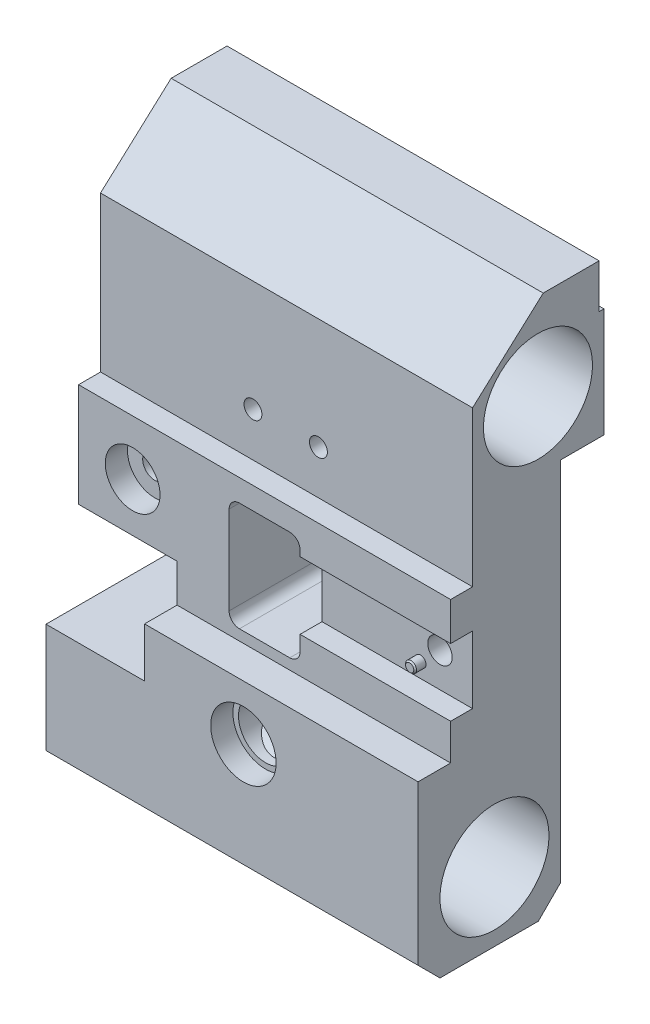
SolidWorks part; units mm, degrees
material "1060 Alloy"
ref_plane "Front Plane" through (0, 0, 0) normal (0, 0, 1) x (1, 0, 0)
ref_plane "Top Plane" through (0, 0, 0) normal (0, 1, 0) x (1, 0, 0)
ref_plane "Right Plane" through (0, 0, 0) normal (1, 0, 0) x (0, 0, -1)
sketch "Sketch1" plane through (0, 0, 0) normal (1, 0, 0) x (0, 0, -1)
  line L0 (14.15, 137.2) -> (30.37, 137.2)
  line L1 (30.37, 137.2) -> (30.37, 124.41)
  line L2 (30.37, 124.41) -> (31.79, 124.41)
  line L3 (31.79, 124.41) -> (31.79, 92.72)
  line L4 (31.79, 92.72) -> (19.1, 92.72)
  line L5 (19.1, 92.72) -> (19.1, -13.636)
  line L6 (19.1, -13.636) -> (12.736, -20)
  line L7 (12.736, -20) -> (-15.816, -20)
  line L8 (-15.816, -20) -> (-22.18, -13.636)
  line L9 (-22.18, -13.636) -> (-22.18, 32.5)
  line L10 (-22.18, 32.5) -> (-12.73, 32.5)
  line L11 (-12.73, 32.5) -> (-12.73, 73.61)
  line L12 (-12.73, 73.61) -> (-6.36, 73.61)
  line L13 (-6.36, 73.61) -> (-6.36, 118.61)
  line L14 (-6.36, 118.61) -> (14.15, 137.2)
  line L15 (-22.18, 32.5) -> (-22.18, 137.2) construction
  line L16 (-22.18, 137.2) -> (14.15, 137.2) construction
  line L17 (30.37, 137.2) -> (31.79, 137.2) construction
  line L18 (31.79, 137.2) -> (31.79, 124.41) construction
  line L19 (31.79, 92.72) -> (31.79, -20) construction
  line L20 (31.79, -20) -> (12.736, -20) construction
  line L21 (-22.18, -13.636) -> (-22.18, -20) construction
  line L22 (-22.18, -20) -> (-15.816, -20) construction
  line L23 (-22.18, 0) -> (31.79, 0) construction
  line L24 (0, -20) -> (0, 17.0401) construction
  line L25 (-22.18, -13.636) -> (19.1, -13.636) construction
  line L26 (0, -15.83) -> (46.0148, -15.83) construction
  line L27 (15.83, 0) -> (15.83, 26.825) construction
  line L28 (0, 15.83) -> (31.79, 15.83) construction
  line L29 (12.625, 111.985) -> (46.8932, 111.985) construction
  line L30 (12.625, 127.815) -> (56.5516, 127.815) construction
  line L31 (12.625, 96.155) -> (52.1782, 96.155) construction
  line L32 (30.37, 124.41) -> (30.37, 97.4751) construction
  line L33 (-15.83, 0) -> (-15.83, 21.2691) construction
  circle A0 centre (0, 0) radius 15.83
  circle A1 centre (12.625, 111.985) radius 15.83
  dimension "D19" = 111.985
  dimension "D14" = 31.66
  dimension "D1" = 41.28
  dimension "D2" = 38.15
  dimension "D3" = 157.2
  dimension "D4" = 44.48
  dimension "D5" = 1.42
  dimension "D6" = 31.69
  dimension "D7" = 25.46
  dimension "D8" = 31.83
  dimension "D9" = 52.5
  dimension "D10" = 93.61
  dimension "D11" = 9
  dimension "D12" = 12.625
  dimension "D13" = 16.22
  dimension "D15" = 45
  dimension "D16" = 3.27
  dimension "D17" = 6.35
  dimension "D18" = 4.17
extrude "Boss-Extrude1" add sketch "Sketch1" along normal blind 54 and the other way blind 54
sketch "Sketch2" plane through (0, 0, -19.1) normal (0, 0, -1) x (-1, 0, 0)
  line L0 (54, -13.636) -> (54, 92.72) construction
  line L1 (-7.3, 67.2) -> (7.3, 67.2)
  line L2 (-10.3, 64.2) -> (-10.3, 38.6)
  line L3 (-7.3, 35.6) -> (7.3, 35.6)
  line L4 (10.3, 64.2) -> (10.3, 38.6)
  line L5 (54, 43.53) -> (25.4, 43.53)
  line L6 (54, 43.53) -> (54, 18.13)
  line L7 (54, 18.13) -> (25.4, 18.13)
  line L8 (25.4, 43.53) -> (25.4, 18.13)
  line L9 (-9.25, 86.37) -> (9.75, 86.37) construction
  line L10 (-10.3, 64.2) -> (-10.3, 67.2) construction
  line L11 (-10.3, 67.2) -> (-7.3, 67.2) construction
  line L12 (7.3, 67.2) -> (10.3, 67.2) construction
  line L13 (10.3, 67.2) -> (10.3, 64.2) construction
  line L14 (10.3, 38.6) -> (10.3, 35.6) construction
  line L15 (10.3, 35.6) -> (7.3, 35.6) construction
  line L16 (-7.3, 35.6) -> (-10.3, 35.6) construction
  line L17 (-10.3, 35.6) -> (-10.3, 38.6) construction
  line L18 (-54, -13.636) -> (-54, 92.72) construction
  line L19 (54, -20) -> (-54, -20) construction
  line L21 (54, 137.2) -> (-54, 137.2) construction
  line L22 (-3.3, 16.595) -> (-3.3, 92.72) construction
  line L25 (54, 92.72) -> (-54, 92.72) construction
  line L26 (9.75, 86.37) -> (9.75, 92.72) construction
  line L27 (-9.25, 86.37) -> (-9.25, 92.72) construction
  line L28 (38.3, 57.72) -> (38.3, 92.72) construction
  line L29 (-44.55, 52.92) -> (-44.55, 92.72) construction
  circle A0 centre (-3.3, 16.595) radius 7.875
  circle A1 centre (-44.55, 52.92) radius 5.5 construction
  circle A2 centre (38.3, 57.72) radius 5.55 construction
  circle A3 centre (-9.25, 86.37) radius 2.6
  circle A4 centre (9.75, 86.37) radius 2.6
  circle A5 centre (-3.3, 16.595) radius 9.42 construction
  circle A6 centre (-9.25, 86.37) radius 4.425 construction
  circle A7 centre (9.75, 86.37) radius 4.425 construction
  circle A8 centre (38.3, 57.72) radius 3.525
  circle A9 centre (-44.55, 52.92) radius 3.55
  arc A10 (-7.3, 35.6) -> (-10.3, 38.6) centre (-7.3, 38.6) cw
  arc A11 (7.3, 35.6) -> (10.3, 38.6) centre (7.3, 38.6) ccw
  arc A12 (7.3, 67.2) -> (10.3, 64.2) centre (7.3, 64.2) cw
  arc A13 (-7.3, 67.2) -> (-10.3, 64.2) centre (-7.3, 64.2) ccw
  dimension "D1" = 3
  dimension "D17" = 18.84
  dimension "D18" = 15.75
  dimension "D20" = 8.85
  dimension "D21" = 5.2
  dimension "D22" = 7.05
  dimension "D23" = 11.1
  dimension "D24" = 7.1
  dimension "D25" = 11
  dimension "D2" = 43.7
  dimension "D3" = 43.7
  dimension "D4" = 55.6
  dimension "D5" = 70
  dimension "D6" = 38.13
  dimension "D7" = 25.4
  dimension "D8" = 28.6
  dimension "D9" = 15.7
  dimension "D10" = 44.25
  dimension "D11" = 63.25
  dimension "D12" = 9.45
  dimension "D13" = 50.7
  dimension "D14" = 35
  dimension "D15" = 6.35
  dimension "D16" = 39.8
  dimension "D19" = 76.125
extrude "Cut-Extrude1" cut sketch "Sketch2" against normal through all
sketch "Sketch3" plane through (0, 0, 12.73) normal (0, 0, 1) x (1, 0, 0)
  line L0 (54, 73.61) -> (54, 32.5) construction
  line L1 (54, 43) -> (10.3, 43)
  line L2 (54, 43) -> (54, 62.52)
  line L3 (54, 62.52) -> (10.3, 62.52)
  line L4 (10.3, 43) -> (10.3, 62.52)
  line L5 (10.3, 38.6) -> (10.3, 64.2) construction
  line L6 (-25.4, 32.5) -> (54, 32.5) construction
  dimension "D1" = 10.5
  dimension "D2" = 19.52
extrude "Cut-Extrude2" cut sketch "Sketch3" against normal blind 6.36
sketch "Sketch4" plane through (0, 0, 6.37) normal (0, 0, 1) x (1, 0, 0)
  line L0 (40.5, 47.335) -> (54, 47.335) construction
  line L2 (54, 43) -> (54, 62.52) construction
  line L3 (38.915, 48.92) -> (38.915, 62.52) construction
  line L4 (54, 62.52) -> (10.3, 62.52) construction
  circle A0 centre (38.915, 47.335) radius 1.585
  dimension "D1" = 3.17
  dimension "D2" = 13.5
  dimension "D3" = 13.6
extrude "Boss-Extrude2" add sketch "Sketch4" along normal blind 3.15
sketch "Sketch10" plane through (0, 0, -19.1) normal (0, 0, -1) x (-1, 0, 0)
  circle A1 centre (-38.915, 47.335) radius 1.585
  circle A2 centre (-38.915, 47.335) radius 1.585
  dimension "D1" = 0
extrude "Cut-Extrude6" cut sketch "Sketch10" against normal blind 20
sketch "Sketch11" plane through (0, 0, -19.1) normal (0, 0, -1) x (-1, 0, 0)
  circle A0 centre (38.3, 57.72) radius 5.5
  circle A1 centre (-44.55, 52.92) radius 5.42
  circle A2 centre (-9.25, 86.37) radius 4.55
  circle A3 centre (9.75, 86.37) radius 4.55
  circle M11 centre (38.3, 57.72) radius 3.525
  circle M12 centre (9.75, 86.37) radius 2.6
  circle M13 centre (-9.25, 86.37) radius 2.6
  dimension "D1" = 10.84
  dimension "D2" = 11
  dimension "D3" = 9.1
extrude "Cut-Extrude7" cut sketch "Sketch11" against normal blind 6.56 contours A0 M11 | A1 region at (-32.9556, 57.72, -19.1)
chamfer "Chamfer1" distance 0.4 angle 45 1 edges at (40.5, 47.335, 9.52)
sketch "Sketch5" plane through (0, 0, 12.73) normal (0, 0, 1) x (1, 0, 0)
  circle A0 centre (-38.3, 57.72) radius 7.945
  dimension "D1" = 15.89
extrude "Cut-Extrude3" cut sketch "Sketch5" against normal blind 6.44
sketch "Sketch6" plane through (0, 0, 22.18) normal (0, 0, 1) x (1, 0, 0)
  circle A0 centre (3.3, 16.595) radius 9.495
  dimension "D1" = 18.99
extrude "Cut-Extrude4" cut sketch "Sketch6" against normal blind 6.44
sketch "Sketch7" plane through (0, 0, -19.1) normal (0, 0, -1) x (-1, 0, 0)
  line L0 (25.4, 43.53) -> (25.4, 18.13) construction
  line L1 (25.4, 34.07) -> (16.63, 34.07)
  line L2 (25.4, 34.07) -> (25.4, -0.89)
  line L3 (25.4, -0.89) -> (16.63, -0.89)
  line L4 (16.63, 34.07) -> (16.63, -0.89)
  line L5 (54, 92.72) -> (-54, 92.72) construction
  dimension "D1" = 8.77
  dimension "D2" = 34.96
  dimension "D3" = 58.65
extrude "Boss-Extrude3" add sketch "Sketch7" along normal blind 3.1
sketch "Sketch8" plane through (0, 0, -22.2) normal (0, 0, -1) x (-1, 0, 0)
  line L0 (21.4, 3.82) -> (21.4, 92.72) construction
  line L1 (54, 92.72) -> (-54, 92.72) construction
  line L2 (16.63, -0.89) -> (25.4, -0.89) construction
  line L5 (25.4, -0.89) -> (25.4, 34.07) construction
  circle A0 centre (21.4, 29.135) radius 2
  circle A1 centre (21.4, 3.82) radius 2
  dimension "D2" = 4
  dimension "D1" = 4
  dimension "D3" = 4.71
  dimension "D4" = 30.025
extrude "Cut-Extrude5" cut sketch "Sketch8" against normal blind 15
extrude "Cut-Extrude8" cut sketch "Sketch11<3>" against normal blind 5.45 contours A2 M13 | A3 M12 region at (13.6713, 86.37, -19.1) region at (-5.3287, 86.37, -19.1)
sketch "Sketch11<3>" plane through (0, 0, -19.1) normal (0, 0, -1) x (-1, 0, 0) same geometry as "Sketch11"
sketch "Sketch12" plane through (0, 0, -19.1) normal (0, 0, -1) x (-1, 0, 0)
  circle A0 centre (-3.3, 16.595) radius 9.475
  dimension "D1" = 18.95
extrude "Cut-Extrude9" cut sketch "Sketch12" against normal blind 5.15
sketch "Sketch13" plane through (0, 0, -19.1) normal (0, 0, -1) x (-1, 0, 0)
  line L0 (-17.6348, 41.72) -> (20.3, 41.72) construction
  line L1 (-13.5, 41.72) -> (-13.5, 73.72) construction
  line L2 (13.2, 41.72) -> (13.2, 73.72) construction
  line L3 (-13.5, 73.72) -> (13.2, 73.72) construction
  line L4 (54, 92.72) -> (-54, 92.72) construction
  line L5 (-54, -13.636) -> (-54, 92.72) construction
  circle A0 centre (-13.5, 73.72) radius 2
  circle A1 centre (13.2, 73.72) radius 2
  circle A2 centre (-13.5, 41.72) radius 2
  circle A3 centre (13.2, 41.72) radius 2
  circle A4 centre (20.3, 41.72) radius 2
  circle A5 centre (-21, 41.92) radius 2
  circle A6 centre (21.4, 29.135) radius 2 construction
  dimension "D3" = 40.5
  dimension "D1" = 51
  dimension "D2" = 19
  dimension "D4" = 67.2
  dimension "D5" = 33
  dimension "D6" = 0.2
  dimension "D7" = 74.3
sketch "Sketch14" plane through (0, 0, -30.37) normal (0, 0, -1) x (-1, 0, 0)
  line L0 (-0.2, 130.91) -> (-0.2, 124.41) construction
  line L1 (54, 124.41) -> (-54, 124.41) construction
  line L2 (-0.2, 130.91) -> (-54, 130.91) construction
  line L3 (-54, 124.41) -> (-54, 137.2) construction
  circle A0 centre (-0.2, 130.91) radius 2
  circle A1 centre (13.2, 73.72) radius 2 construction
  dimension "D1" = 53.8
  dimension "D2" = 6.5
extrude "Cut-Extrude10" cut sketch "Sketch13" against normal blind 10
extrude "Cut-Extrude11" cut sketch "Sketch14" against normal blind 10
ref_axis "Axis1" through (-54, 111.985, -12.625) along (1, 0, 0)
ref_axis "Axis2" through (-54, 0, 0) along (1, 0, 0)
